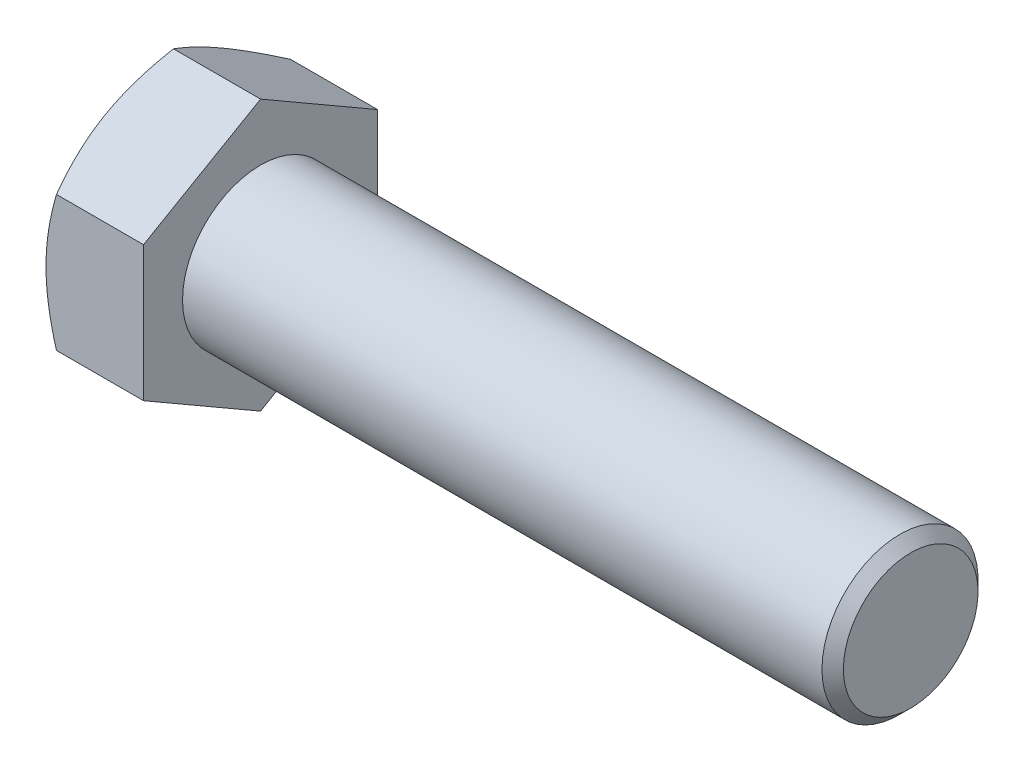
SolidWorks part; units mm, degrees
ref_plane "Front Plane" through (0, 0, 0) normal (0, 0, 1) x (1, 0, 0)
ref_plane "Top Plane" through (0, 0, 0) normal (0, 1, 0) x (1, 0, 0)
ref_plane "Right Plane" through (0, 0, 0) normal (1, 0, 0) x (0, 0, -1)
sketch "BaseHeadSke" plane through (0, 0, 0) normal (1, 0, 0) x (0, 0, -1)
  line L1 (0, 20.7846) -> (-18, 10.3923)
  line L2 (-18, 10.3923) -> (-18, -10.3923)
  line L3 (-18, -10.3923) -> (0, -20.7846)
  line L4 (0, -20.7846) -> (18, -10.3923)
  line L5 (18, -10.3923) -> (18, 10.3923)
  line L6 (18, 10.3923) -> (0, 20.7846)
  circle A0 centre (0, 0) radius 18 construction
extrude "BaseHead" add sketch "BaseHeadSke" along normal blind 15
sketch "HeadChamferSke" plane through (0, 0, 0) normal (0, 0, 1) x (1, 0, 0)
  line L0 (0, 0) -> (24.6933, 0) construction
  line L1 (0, 10.3923) -> (0, -10.3923) construction
  line L2 (0, 20.7846) -> (0, 18)
  line L3 (0, 18) -> (1.6077, 20.7846)
  line L4 (1.6077, 20.7846) -> (0, 20.7846)
  line L9 (15, 20.7846) -> (0, 20.7846) construction
  dimension "Angle_Chamfer_Head" = 30
revolve "HeadChamfer" cut sketch "HeadChamferSke" angle 360 about L0
sketch "BodySke" plane through (0, 0, 0) normal (0, 0, 1) x (1, 0, 0)
  line L0 (0, 0) -> (115, 0)
  line L1 (0, 10.3923) -> (0, -10.3923) construction
  line L2 (0, 0) -> (140.1681, 0) construction
  line L3 (115, 0) -> (115, 10.352)
  line L4 (113.352, 12) -> (0, 12)
  line L5 (0, 12) -> (0, 0)
  line L6 (15, 10.3923) -> (15, -10.3923) construction
  line L7 (18, 16.3011) -> (18, 0) construction
  line L8 (61, 16.3011) -> (61, 0) construction
  line L9 (113.352, 12) -> (115, 10.352)
  dimension "Thread_minor" = 20.704
  dimension "Thread_length" = 54
revolve "BaseBody" add sketch "BodySke" angle 360 about L2
cosmetic thread "ThreadCosmetic" [suppressed] parameters "Thread_length"=54, "Thread_minor"=20.704
sketch "BearingFaceSke" plane through (0, 0, 0) normal (0, 0, 1) x (1, 0, 0)
  line L0 (0, 0) -> (132.5635, 0) construction
  line L1 (0, 10.3923) -> (0, -10.3923) construction
  line L2 (15, 20.7846) -> (15, 10.3923) construction
  line L3 (15, 18) -> (14.2, 18)
  line L4 (15, 18) -> (15, 28)
  line L5 (15, 28) -> (14.2, 28)
  line L6 (14.2, 18) -> (14.2, 28)
  dimension "D1" = 36
  dimension "D2" = 10
revolve "BearingFace" [suppressed] cut sketch "BearingFaceSke" angle 360 about L0
fillet "HeadFillet" [suppressed] radius 0.8
sketch "ThdSchSke" plane through (0, 0, 0) normal (0, 0, 1) x (1, 0, 0)
  line L0 (0, 0) -> (118.9221, 0) construction
  line L1 (0, 10.3923) -> (0, -10.3923) construction
  line L2 (110.352, 13.9029) -> (110.352, 12)
  line L3 (110.352, 13.9029) -> (112.2549, 13.9029)
  line L4 (112.2549, 13.9029) -> (112.2549, 12)
  line L5 (112.2549, 12) -> (111.3035, 10.352)
  line L6 (111.3035, 10.352) -> (110.352, 12)
  dimension "D1" = 3
revolve "ThreadSchematic" [suppressed] cut sketch "ThdSchSke" angle 360 about L0
pattern_linear "ThdSchPat" [suppressed] of bodies 116
equation "\"D1@BearingFaceSke\" = \"Width_flats@BaseHeadSke\""
equation "\"Thread_minor@ThreadCosmetic\" = \"Thread_minor@BodySke\""
equation "\"Thread_length@ThreadCosmetic\" = \"Thread_length@BodySke\""
equation "\"D1@ThdSchSke\" = \"Advance@BodySke\""
equation "\"Tooth_Num@ThdSchPat\" = int( \"Thread_length@BodySke\" / \"Advance@BodySke\" )  -1"
equation "\"D3@ThdSchPat\" = \"Advance@BodySke\""
